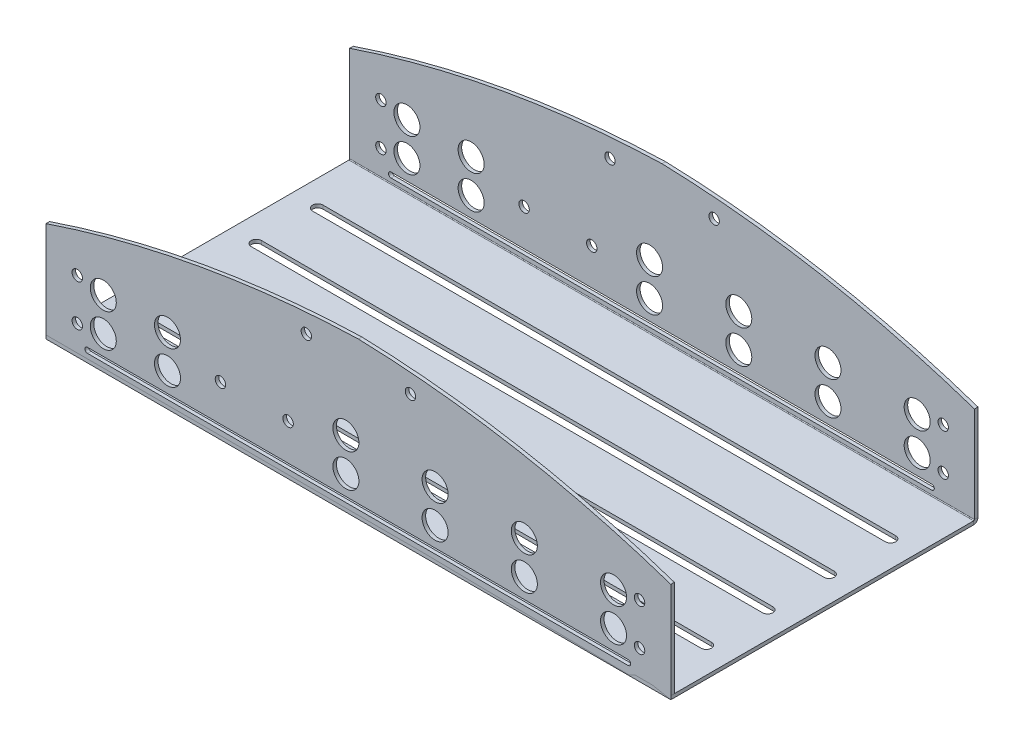
SolidWorks part; units mm, degrees
note: The reader was unsure of these and kept them because the rebuilt part matched: flange length of "Edge-Flange1".
material "1060 Alloy"
ref_plane "Front Plane" through (0, 0, 0) normal (0, 0, 1) x (1, 0, 0)
ref_plane "Top Plane" through (0, 0, 0) normal (0, 1, 0) x (1, 0, 0)
ref_plane "Right Plane" through (0, 0, 0) normal (1, 0, 0) x (0, 0, -1)
sketch "Sketch1" plane through (0, 0, 0) normal (0, 0, 1) x (1, 0, 0)
  line L0 (0, -56.3472) -> (0, 39.6528)
  line L1 (0, -56.3472) -> (-600, -56.3472)
  line L2 (-600, -56.3472) -> (-600, 39.6528)
  line L3 (-300, -56.3472) -> (-300, 93.6528) construction
  line L4 (-600, 39.6528) -> (0, 39.6528) construction
  line L5 (-55, -56.3472) -> (-55, -24.3472) construction
  line L6 (-55, -24.3472) -> (-55, 7.6528) construction
  line L7 (-483.3333, -56.3472) -> (-483.3333, 71.6528) construction
  line L8 (-116.6667, -56.3472) -> (-116.6667, 71.6528) construction
  line L9 (-483.3333, 71.6528) -> (-116.6667, 71.6528) construction
  line L10 (-300, 93.6528) -> (-350, 93.6528) construction
  line L11 (-350, 90.9488) -> (-350, 72.9488) construction
  line L12 (-570, -8.3472) -> (-600, -8.3472) construction
  line L13 (-545, 7.6528) -> (-545, -24.3472) construction
  line L14 (-570, -28.3472) -> (-570, 11.6528) construction
  line L15 (-570, -8.3472) -> (-400, -8.3472) construction
  line L16 (-30, -28.3472) -> (-30, 11.6528) construction
  line L17 (-400, -8.3472) -> (-367.5, -8.3472) construction
  line L18 (-30, -8.3472) -> (0, -8.3472) construction
  line L19 (-400, -8.3472) -> (-400, -56.3472) construction
  circle A0 centre (-55, 7.6528) radius 12.5
  circle A1 centre (-55, -24.3472) radius 12.5
  circle A2 centre (-545, 7.6528) radius 12.5
  circle A3 centre (-545, -24.3472) radius 12.5
  circle A4 centre (-140.6667, 7.6528) radius 12.5
  circle A5 centre (-140.6667, -24.3472) radius 12.5
  circle A6 centre (-226.3333, 7.6528) radius 12.5
  circle A7 centre (-226.3333, -24.3472) radius 12.5
  circle A8 centre (-312, 7.6528) radius 12.5
  circle A9 centre (-312, -24.3472) radius 12.5
  arc A10 (-600, 39.6528) -> (-300, 93.6528) centre (-269.3317, -937.0599) cw
  arc A11 (0, 39.6528) -> (-300, 93.6528) centre (-330.6683, -937.0599) ccw
  circle A12 centre (-483.3333, 7.6528) radius 12.5
  circle A13 centre (-483.3333, -24.3472) radius 12.5
  circle A14 centre (-397.6667, 7.6528) radius 12.5 [skipped]
  circle A15 centre (-397.6667, -24.3472) radius 12.5 [skipped]
  circle A16 centre (-350, 72.9488) radius 5
  circle A17 centre (-250, 72.9488) radius 5
  circle A18 centre (-30, 11.6528) radius 5
  circle A20 centre (-30, -28.3472) radius 5
  circle A22 centre (-570, -28.3472) radius 5
  circle A23 centre (-570, 11.6528) radius 5
  circle A24 centre (-367.5, -8.3472) radius 5
  circle A25 centre (-432.5, -8.3472) radius 5
  point P64 (-30, -8.3472)
  dimension "D6" = 55
  dimension "D9" = 50
  dimension "D10" = 18
  dimension "D11" = 30
  dimension "D13" = 10
  dimension "D1" = 150
  dimension "D2" = 96
  dimension "D3" = 600
  dimension "D4" = 20
  dimension "D5" = 200
  dimension "D8" = 128
  dimension "D12" = 32.5
  dimension "D7" = 6
base flange "Base-Flange1" sketch "Sketch1" thickness 3.4 reverse thickness direction no parameters "D1"=0.7366
edge flange "Edge-Flange1" sketch "Sketch8" flange angle 90 flange length 295 flange position material inside bend radius 0.7366 thickness 3.4 relief rectangular parameters "D6"=10
sketch "Sketch8" plane through (0, -56.3472, 0) normal (0, 1, 0) x (-1, 0, 0)
  line L1 (600, 0) -> (0, 0) construction
  line L2 (0, 0) -> (0, 291.6)
  line L3 (0, 291.6) -> (600, 291.6)
  line L4 (600, 291.6) -> (600, 0)
  line L5 (600, 0) -> (0, 0)
bend "EdgeBend1" bend radius 0.7366 bend angle 90 parameters "D5"=1
sketch "Sketch9" plane through (0, 0, 291.6) normal (0, 0, 1) x (1, 0, 0)
  line L3 (0, -56.3472) -> (0, 39.6528)
  line L4 (-600, 39.6528) -> (-600, -56.3472)
  line L5 (-600, -56.3472) -> (0, -56.3472)
  line L6 (0, -56.3472) -> (0, 39.6528)
  line L7 (-600, 39.6528) -> (-600, -56.3472)
  line L8 (-600, -56.3472) -> (0, -56.3472)
  circle A0 centre (-350, 72.9488) radius 5 construction
  circle A1 centre (-545, 7.6528) radius 12.5
  circle A2 centre (-545, 7.6528) radius 12.5
  circle A3 centre (-55, -24.3472) radius 12.5
  circle A4 centre (-55, -24.3472) radius 12.5
  circle A5 centre (-55, 7.6528) radius 12.5
  circle A6 centre (-55, 7.6528) radius 12.5
  circle A7 centre (-312, -24.3472) radius 12.5
  arc A8 (0, 39.6528) -> (-300, 93.6528) centre (-330.6683, -937.0599) ccw
  arc A9 (-300, 93.6528) -> (-600, 39.6528) centre (-269.3317, -937.0599) ccw
  arc A10 (0, 39.6528) -> (-300, 93.6528) centre (-330.6683, -937.0599) ccw
  arc A11 (-300, 93.6528) -> (-600, 39.6528) centre (-269.3317, -937.0599) ccw
  circle A12 centre (-312, -24.3472) radius 12.5
  circle A13 centre (-312, 7.6528) radius 12.5
  circle A14 centre (-312, 7.6528) radius 12.5
  circle A15 centre (-226.3333, -24.3472) radius 12.5
  circle A16 centre (-226.3333, -24.3472) radius 12.5
  circle A17 centre (-226.3333, 7.6528) radius 12.5
  circle A18 centre (-226.3333, 7.6528) radius 12.5
  circle A19 centre (-140.6667, -24.3472) radius 12.5
  circle A20 centre (-140.6667, -24.3472) radius 12.5
  circle A21 centre (-140.6667, 7.6528) radius 12.5
  circle A22 centre (-140.6667, 7.6528) radius 12.5
  circle A23 centre (-545, -24.3472) radius 12.5
  circle A24 centre (-545, -24.3472) radius 12.5
  circle A25 centre (-483.3333, -24.3472) radius 12.5
  circle A26 centre (-483.3333, -24.3472) radius 12.5
  circle A27 centre (-483.3333, 7.6528) radius 12.5
  circle A28 centre (-483.3333, 7.6528) radius 12.5
  circle A29 centre (-250, 72.9488) radius 5 construction
  circle A30 centre (-350, 72.9488) radius 5
  circle A31 centre (-250, 72.9488) radius 5
  circle A32 centre (-30, 11.6528) radius 5 construction
  circle A33 centre (-30, -28.3472) radius 5 construction
  circle A36 centre (-30, 11.6528) radius 5
  circle A37 centre (-30, -28.3472) radius 5
  circle A38 centre (-570, -28.3472) radius 5 construction
  circle A39 centre (-570, -28.3472) radius 5
  circle A40 centre (-570, 11.6528) radius 5 construction
  circle A41 centre (-570, 11.6528) radius 5
  circle A42 centre (-432.5, -8.3472) radius 5 construction
  circle A43 centre (-432.5, -8.3472) radius 5
  circle A44 centre (-367.5, -8.3472) radius 5 construction
  circle A45 centre (-367.5, -8.3472) radius 5
  dimension "D1" = 0
  dimension "D2" = 0
  dimension "D3" = 0
  dimension "D4" = 0
  dimension "D5" = 0
  dimension "D6" = 0
  dimension "D7" = 0
  dimension "D8" = 0
  dimension "D9" = 0
  dimension "D10" = 0
  dimension "D11" = 0
  dimension "D12" = 0
  dimension "D13" = 0
base flange "Base-Flange3" sketch "Sketch9" thickness 3.4 reverse thickness direction no parameters "D1"=0.7366
sketch "Sketch10" plane through (0, -56.3472, 0) normal (0, -1, 0) x (1, 0, 0)
  line L0 (-600, 291.6) -> (0, 291.6) construction
  line L1 (-600, 291.6) -> (0, 291.6) construction
  line L2 (-300, 291.6) -> (-300, -3.4) construction
  line L3 (0, -3.4) -> (-600, -3.4) construction
  line L4 (-575, 237.6) -> (-25, 237.6)
  line L6 (-25, 227.6) -> (-575, 227.6)
  line L7 (0, 291.6) -> (0, 0.7366) construction
  arc A0 (-25, 227.6) -> (-25, 237.6) centre (-25, 232.6) ccw
  arc A1 (-575, 227.6) -> (-575, 237.6) centre (-575, 232.6) cw
  point P13 (0, 0)
  point P16 (0, 0)
  point P19 (-300, 237.6)
  point P20 (-300, 227.6)
  dimension "D1" = 10
  dimension "D2" = 59
  dimension "D3" = 25
extrude "Cut-Extrude1" cut sketch "Sketch10" against normal up to next (3.4 mm away)
sketch "Sketch11" plane through (0, 0, 291.6) normal (0, 0, 1) x (1, 0, 0)
  line L0 (-601.3113, 39.6528) -> (0, 39.6528) construction
  line L1 (-300.6557, 39.6528) -> (-300.6557, -58.3813) construction
  line L2 (-560.2332, -43.3472) -> (-41.0781, -43.3472)
  line L3 (-41.0781, -48.3472) -> (-560.2332, -48.3472)
  arc A2 (-41.0781, -48.3472) -> (-41.0781, -43.3472) centre (-41.0781, -45.8472) ccw
  arc A3 (-560.2332, -48.3472) -> (-560.2332, -43.3472) centre (-560.2332, -45.8472) cw
  point P7 (-375.3315, -48.3472)
  point P8 (-40.1574, -45.8472)
  point P10 (-300.6557, -43.3472)
  point P11 (-300.6557, -48.3472)
  point P12 (0, 0)
  point P13 (-41.0781, -45.8472)
  point P18 (-41.0781, -45.8472)
  dimension "D1" = 5
  dimension "D2" = 83
extrude "Cut-Extrude2" cut sketch "Sketch11" against normal through all
pattern_linear "LPattern1" count 4 spacing 59 along (0, 0, -1) of "Cut-Extrude1"
sketch "Bend-Lines1" [suppressed] plane through (0, 0, 0) normal (0, 1, 0) x (1, 0, 0)
sketch "Bounding-Box1" [suppressed] plane through (0, 0, 0) normal (0, 1, 0) x (1, 0, 0)
sheet metal parameters "Sheet-Metal1" thickness 3.4 parameters "D1"=0.7366
flat pattern "Flat-Pattern1" [suppressed]
sketch "Bend-Lines2" plane through (0, 0, 0) normal (0, 1, 0) x (1, 0, 0)
sketch3d "Bounding-Box2" [suppressed]
  line L0 (330.6683, 880.7128, 0) -> (-269.3317, 880.7128, 0) construction
  line L1 (330.6683, 1030.7128, 0) -> (-269.3317, 1030.7128, 0) construction
  line L2 (330.6683, 880.7128, 0) -> (330.6683, 1030.7128, 0) construction
  line L3 (-269.3317, 880.7128, 0) -> (-269.3317, 1030.7128, 0) construction
sheet metal parameters "Sheet-Metal2" thickness 3.4 parameters "D1"=0.7366
flat pattern "Flat-Pattern1"
sketch "Bend-Lines2" plane through (0, 0, 0) normal (0, 0, 1) x (1, 0, 0)
  line L0 (-600, -54.1243) -> (0, -54.1243) construction
  line L1 (-600, -54.1243) -> (0, -54.1243) construction
sketch3d "Bounding-Box2" [suppressed]
  line L0 (-330.6683, 590.1586, 0) -> (269.3317, 590.1586, 0) construction
  line L1 (-330.6683, 1030.7128, 0) -> (269.3317, 1030.7128, 0) construction
  line L2 (-330.6683, 590.1586, 0) -> (-330.6683, 1030.7128, 0) construction
  line L3 (269.3317, 590.1586, 0) -> (269.3317, 1030.7128, 0) construction
bend of the flat pattern "Flatten-<EdgeBend1>1"
sheet metal parameters "Sheet-Metal4" thickness 3.4 parameters "D1"=0.7366
flat pattern "Flat-Pattern4"
sketch "Bend-Lines4" plane through (0, 0, 0) normal (0, 1, 0) x (1, 0, 0)
sketch3d "Bounding-Box4" [suppressed]
  line L0 (-269.3317, 880.7128, 0) -> (330.6683, 880.7128, 0) construction
  line L1 (-269.3317, 1030.7128, 0) -> (330.6683, 1030.7128, 0) construction
  line L2 (-269.3317, 880.7128, 0) -> (-269.3317, 1030.7128, 0) construction
  line L3 (330.6683, 880.7128, 0) -> (330.6683, 1030.7128, 0) construction
sheet metal parameters "Sheet-Metal5" thickness 3.4 parameters "D1"=0.7366
flat pattern "Flat-Pattern1"
sketch "Bend-Lines2" plane through (0, 0, 0) normal (0, 0, 1) x (1, 0, 0)
  line L0 (-600, -54.1243) -> (0, -54.1243) construction
  line L1 (-600, -54.1243) -> (0, -54.1243) construction
sketch3d "Bounding-Box2" [suppressed]
  line L0 (-330.6683, 590.1586, 0) -> (269.3317, 590.1586, 0) construction
  line L1 (-330.6683, 1030.7128, 0) -> (269.3317, 1030.7128, 0) construction
  line L2 (-330.6683, 590.1586, 0) -> (-330.6683, 1030.7128, 0) construction
  line L3 (269.3317, 590.1586, 0) -> (269.3317, 1030.7128, 0) construction
bend of the flat pattern "Flatten-<EdgeBend1>1"
sheet metal parameters "Sheet-Metal6" thickness 3.4 parameters "D1"=0.7366
flat pattern "Flat-Pattern4"
sketch "Bend-Lines4" plane through (0, 0, 0) normal (0, 1, 0) x (1, 0, 0)
sketch3d "Bounding-Box4" [suppressed]
  line L0 (-269.3317, 880.7128, 0) -> (330.6683, 880.7128, 0) construction
  line L1 (-269.3317, 1030.7128, 0) -> (330.6683, 1030.7128, 0) construction
  line L2 (-269.3317, 880.7128, 0) -> (-269.3317, 1030.7128, 0) construction
  line L3 (330.6683, 880.7128, 0) -> (330.6683, 1030.7128, 0) construction
sheet metal parameters "Sheet-Metal7" thickness 3.4 parameters "D1"=0.7366
flat pattern "Flat-Pattern1"
sketch "Bend-Lines2" plane through (0, 0, 0) normal (0, 0, 1) x (1, 0, 0)
  line L0 (-600, -54.1243) -> (0, -54.1243) construction
  line L1 (-600, -54.1243) -> (0, -54.1243) construction
sketch3d "Bounding-Box2" [suppressed]
  line L0 (-330.6683, 590.1586, 0) -> (269.3317, 590.1586, 0) construction
  line L1 (-330.6683, 1030.7128, 0) -> (269.3317, 1030.7128, 0) construction
  line L2 (-330.6683, 590.1586, 0) -> (-330.6683, 1030.7128, 0) construction
  line L3 (269.3317, 590.1586, 0) -> (269.3317, 1030.7128, 0) construction
bend of the flat pattern "Flatten-<EdgeBend1>1"
sheet metal parameters "Sheet-Metal8" thickness 3.4 parameters "D1"=0.7366
flat pattern "Flat-Pattern1"
sketch "Bend-Lines2" plane through (0, 0, 0) normal (0, 0, 1) x (1, 0, 0)
  line L0 (-600, -54.1243) -> (0, -54.1243) construction
  line L1 (-600, -54.1243) -> (0, -54.1243) construction
sketch3d "Bounding-Box2" [suppressed]
  line L0 (-330.6683, 590.1586, 0) -> (269.3317, 590.1586, 0) construction
  line L1 (-330.6683, 1030.7128, 0) -> (269.3317, 1030.7128, 0) construction
  line L2 (-330.6683, 590.1586, 0) -> (-330.6683, 1030.7128, 0) construction
  line L3 (269.3317, 590.1586, 0) -> (269.3317, 1030.7128, 0) construction
bend of the flat pattern "Flatten-<EdgeBend1>1"
